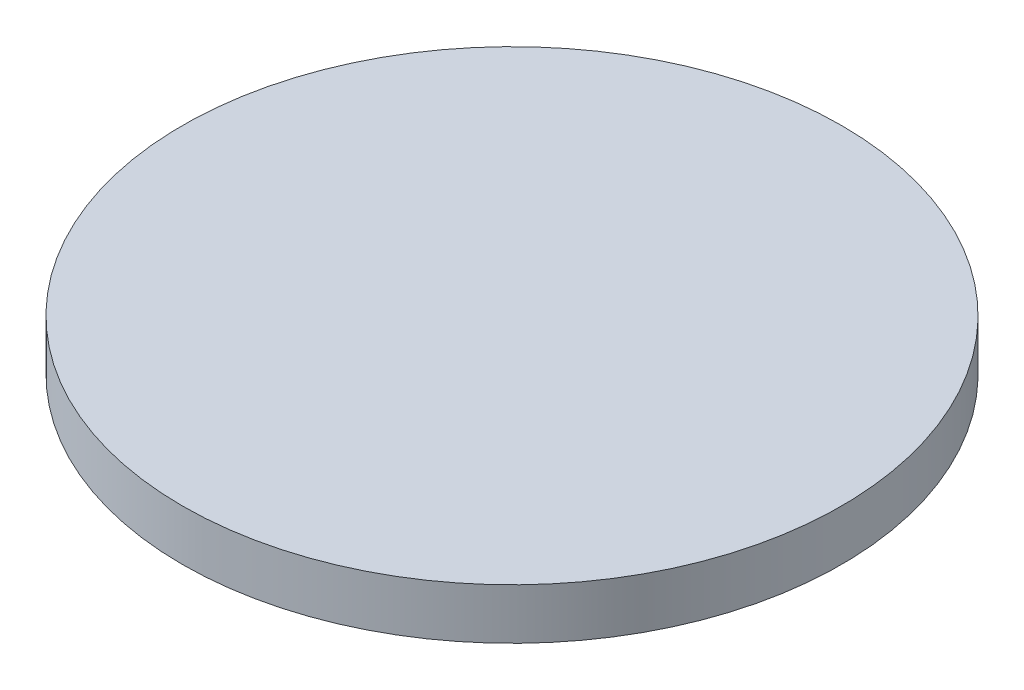
SolidWorks part; units mm, degrees
ref_plane "Ön Düzlem" through (0, 0, 0) normal (0, 0, 1) x (1, 0, 0)
ref_plane "Üst Düzlem" through (0, 0, 0) normal (0, 1, 0) x (1, 0, 0)
ref_plane "Sağ Düzlem" through (0, 0, 0) normal (1, 0, 0) x (0, 0, -1)
sketch "Çizim1" plane through (0, 0, 0) normal (0, 1, 0) x (1, 0, 0)
  circle A0 centre (0, 0) radius 26
extrude "Yükseklik-Ekstrüzyon1" add sketch "Çizim1" along normal blind 4
